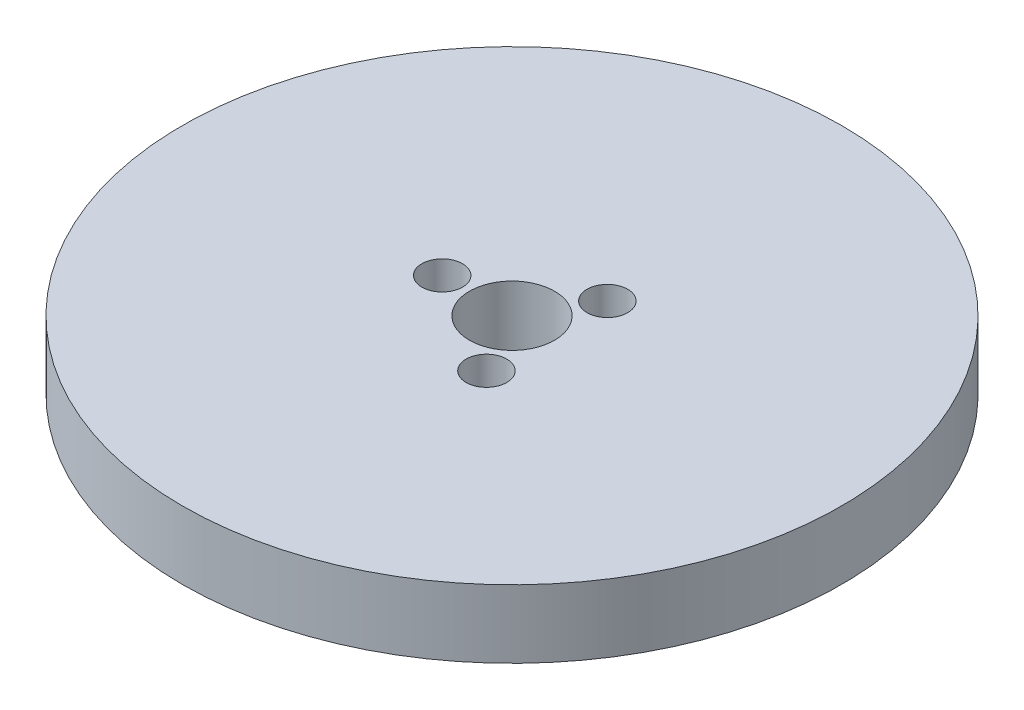
SolidWorks part; units mm, degrees
ref_plane "Front Plane" through (0, 0, 0) normal (0, 0, 1) x (1, 0, 0)
ref_plane "Top Plane" through (0, 0, 0) normal (0, 1, 0) x (1, 0, 0)
ref_plane "Right Plane" through (0, 0, 0) normal (1, 0, 0) x (0, 0, -1)
sketch "Sketch1" plane through (0, 0, 0) normal (0, 1, 0) x (1, 0, 0)
  circle A0 centre (0, 0) radius 77.5
  dimension "FLANGE_OD" = 155
extrude "Boss-Extrude1" add sketch "Sketch1" along normal blind 16
sketch "Sketch2" plane through (0, 0, 0) normal (0, 1, 0) x (1, 0, 0)
  circle A0 centre (0, 0) radius 10
  dimension "BORE_D" = 20
extrude "Cut-Extrude1" cut sketch "Sketch2" along normal through all
sketch "Sketch3" plane through (0, 16, 0) normal (0, 1, 0) x (1, 0, 0)
  circle A0 centre (0, 0) radius 16.4154 construction
  circle A1 centre (-16.4154, 0) radius 4.7837
  dimension "BOLT_D" = 9.5674
  dimension "BOLT_PCD" = 32.8308
extrude "Cut-Extrude2" cut sketch "Sketch3" against normal blind 15.1527
pattern_circular "CirPattern1" count 3 over 360 about axis through (0, 0, 0) along (0, 1, 0) of "Cut-Extrude2"
